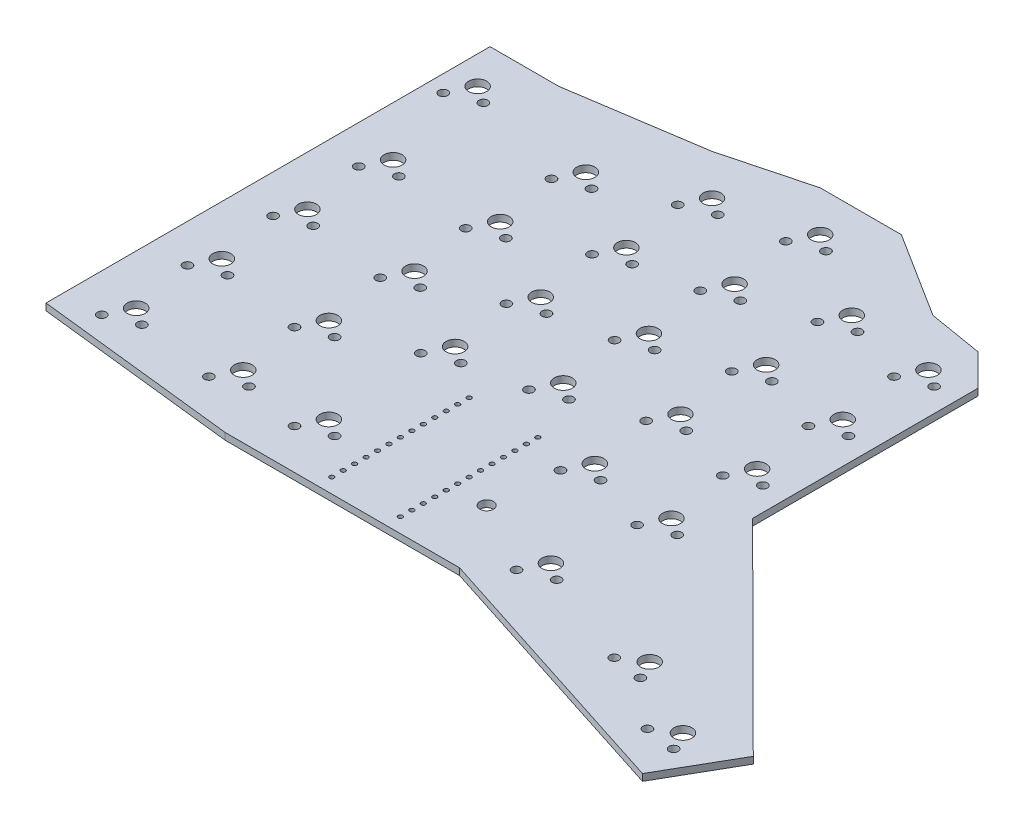
SolidWorks part; units mm, degrees
ref_plane "Front Plane" through (0, 0, 0) normal (0, 0, 1) x (1, 0, 0)
ref_plane "Top Plane" through (0, 0, 0) normal (0, 1, 0) x (1, 0, 0)
ref_plane "Right Plane" through (0, 0, 0) normal (1, 0, 0) x (0, 0, -1)
sketch "Main" plane through (0, 0, 0) normal (0, 1, 0) x (1, 0, 0)
  line L0 (6.46, 3.92) -> (12.81, 6.46) construction
  line L1 (0, 0) -> (18, 0) construction
  line L2 (0, 0) -> (0, 18) construction
  line L3 (0, 18) -> (18, 18) construction
  line L4 (18, 0) -> (18, 18) construction
  line L5 (2, 16) -> (16, 16)
  line L6 (2, 16) -> (2, 2)
  line L7 (2, 2) -> (16, 2)
  line L8 (16, 16) -> (16, 2)
  line L18 (9, 9) -> (6.46, 3.92) construction
  line L20 (9, 9) -> (12.81, 6.46) construction
  line L22 (25.46, 12.92) -> (31.81, 15.46) construction
  line L23 (19, 9) -> (37, 9) construction
  line L24 (19, 9) -> (19, 27) construction
  line L25 (19, 27) -> (37, 27) construction
  line L26 (37, 9) -> (37, 27) construction
  line L27 (21, 25) -> (35, 25)
  line L28 (21, 25) -> (21, 11)
  line L29 (21, 11) -> (35, 11)
  line L30 (35, 25) -> (35, 11)
  line L31 (28, 18) -> (25.46, 12.92) construction
  line L32 (28, 18) -> (31.81, 15.46) construction
  line L33 (44.46, 17.92) -> (50.81, 20.46) construction
  line L34 (38, 14) -> (56, 14) construction
  line L35 (38, 14) -> (38, 32) construction
  line L36 (38, 32) -> (56, 32) construction
  line L37 (56, 14) -> (56, 32) construction
  line L38 (40, 30) -> (54, 30)
  line L39 (40, 30) -> (40, 16)
  line L40 (40, 16) -> (54, 16)
  line L41 (54, 30) -> (54, 16)
  line L42 (47, 23) -> (44.46, 17.92) construction
  line L43 (47, 23) -> (50.81, 20.46) construction
  line L44 (63.46, 5.92) -> (69.81, 8.46) construction
  line L45 (57, 2) -> (75, 2) construction
  line L46 (57, 2) -> (57, 20) construction
  line L47 (57, 20) -> (75, 20) construction
  line L48 (75, 2) -> (75, 20) construction
  line L49 (59, 18) -> (73, 18)
  line L50 (59, 18) -> (59, 4)
  line L51 (59, 4) -> (73, 4)
  line L52 (73, 18) -> (73, 4)
  line L53 (66, 11) -> (63.46, 5.92) construction
  line L54 (66, 11) -> (69.81, 8.46) construction
  line L55 (82.46, 3.92) -> (88.81, 6.46) construction
  line L56 (76, 0) -> (94, 0) construction
  line L57 (76, 0) -> (76, 18) construction
  line L58 (76, 18) -> (94, 18) construction
  line L59 (94, 0) -> (94, 18) construction
  line L60 (78, 16) -> (92, 16)
  line L61 (78, 16) -> (78, 2)
  line L62 (78, 2) -> (92, 2)
  line L63 (92, 16) -> (92, 2)
  line L64 (85, 9) -> (82.46, 3.92) construction
  line L65 (85, 9) -> (88.81, 6.46) construction
  line L88 (2, -3) -> (16, -3)
  line L89 (2, -3) -> (2, -17)
  line L90 (2, -17) -> (16, -17)
  line L91 (16, -3) -> (16, -17)
  line L92 (21, 6) -> (35, 6)
  line L93 (21, 6) -> (21, -8)
  line L94 (21, -8) -> (35, -8)
  line L95 (35, 6) -> (35, -8)
  line L96 (40, 11) -> (54, 11)
  line L97 (40, 11) -> (40, -3)
  line L98 (40, -3) -> (54, -3)
  line L99 (54, 11) -> (54, -3)
  line L100 (59, -1) -> (73, -1)
  line L101 (59, -1) -> (59, -15)
  line L102 (59, -15) -> (73, -15)
  line L103 (73, -1) -> (73, -15)
  line L104 (78, -3) -> (92, -3)
  line L105 (78, -3) -> (78, -17)
  line L106 (78, -17) -> (92, -17)
  line L107 (92, -3) -> (92, -17)
  line L116 (6.46, -15.08) -> (12.81, -12.54) construction
  line L117 (0, -19) -> (18, -19) construction
  line L118 (0, -19) -> (0, -1) construction
  line L119 (0, -1) -> (18, -1) construction
  line L120 (18, -19) -> (18, -1) construction
  line L121 (9, -10) -> (6.46, -15.08) construction
  line L122 (9, -10) -> (12.81, -12.54) construction
  line L123 (25.46, -6.08) -> (31.81, -3.54) construction
  line L124 (19, -10) -> (37, -10) construction
  line L125 (19, -10) -> (19, 8) construction
  line L126 (19, 8) -> (37, 8) construction
  line L127 (37, -10) -> (37, 8) construction
  line L128 (28, -1) -> (25.46, -6.08) construction
  line L129 (28, -1) -> (31.81, -3.54) construction
  line L130 (44.46, -1.08) -> (50.81, 1.46) construction
  line L131 (38, -5) -> (56, -5) construction
  line L132 (38, -5) -> (38, 13) construction
  line L133 (38, 13) -> (56, 13) construction
  line L134 (56, -5) -> (56, 13) construction
  line L135 (47, 4) -> (44.46, -1.08) construction
  line L136 (47, 4) -> (50.81, 1.46) construction
  line L137 (63.46, -13.08) -> (69.81, -10.54) construction
  line L138 (57, -17) -> (75, -17) construction
  line L139 (57, -17) -> (57, 1) construction
  line L140 (57, 1) -> (75, 1) construction
  line L141 (75, -17) -> (75, 1) construction
  line L142 (66, -8) -> (63.46, -13.08) construction
  line L143 (66, -8) -> (69.81, -10.54) construction
  line L144 (82.46, -15.08) -> (88.81, -12.54) construction
  line L145 (76, -19) -> (94, -19) construction
  line L146 (76, -19) -> (76, -1) construction
  line L147 (76, -1) -> (94, -1) construction
  line L148 (94, -19) -> (94, -1) construction
  line L149 (85, -10) -> (82.46, -15.08) construction
  line L150 (85, -10) -> (88.81, -12.54) construction
  line L165 (2, -22) -> (16, -22)
  line L166 (2, -22) -> (2, -36)
  line L167 (2, -36) -> (16, -36)
  line L168 (16, -22) -> (16, -36)
  line L169 (21, -13) -> (35, -13)
  line L170 (21, -13) -> (21, -27)
  line L171 (21, -27) -> (35, -27)
  line L172 (35, -13) -> (35, -27)
  line L173 (40, -8) -> (54, -8)
  line L174 (40, -8) -> (40, -22)
  line L175 (40, -22) -> (54, -22)
  line L176 (54, -8) -> (54, -22)
  line L177 (59, -20) -> (73, -20)
  line L178 (59, -20) -> (59, -34)
  line L179 (59, -34) -> (73, -34)
  line L180 (73, -20) -> (73, -34)
  line L181 (78, -22) -> (92, -22)
  line L182 (78, -22) -> (78, -36)
  line L183 (78, -36) -> (92, -36)
  line L184 (92, -22) -> (92, -36)
  line L193 (6.46, -34.08) -> (12.81, -31.54) construction
  line L194 (0, -38) -> (18, -38) construction
  line L195 (0, -38) -> (0, -20) construction
  line L196 (0, -20) -> (18, -20) construction
  line L197 (18, -38) -> (18, -20) construction
  line L198 (9, -29) -> (6.46, -34.08) construction
  line L199 (9, -29) -> (12.81, -31.54) construction
  line L200 (25.46, -25.08) -> (31.81, -22.54) construction
  line L201 (19, -29) -> (37, -29) construction
  line L202 (19, -29) -> (19, -11) construction
  line L203 (19, -11) -> (37, -11) construction
  line L204 (37, -29) -> (37, -11) construction
  line L205 (28, -20) -> (25.46, -25.08) construction
  line L206 (28, -20) -> (31.81, -22.54) construction
  line L207 (44.46, -20.08) -> (50.81, -17.54) construction
  line L208 (38, -24) -> (56, -24) construction
  line L209 (38, -24) -> (38, -6) construction
  line L210 (38, -6) -> (56, -6) construction
  line L211 (56, -24) -> (56, -6) construction
  line L212 (47, -15) -> (44.46, -20.08) construction
  line L213 (47, -15) -> (50.81, -17.54) construction
  line L214 (63.46, -32.08) -> (69.81, -29.54) construction
  line L215 (57, -36) -> (75, -36) construction
  line L216 (57, -36) -> (57, -18) construction
  line L217 (57, -18) -> (75, -18) construction
  line L218 (75, -36) -> (75, -18) construction
  line L219 (66, -27) -> (63.46, -32.08) construction
  line L220 (66, -27) -> (69.81, -29.54) construction
  line L221 (82.46, -34.08) -> (88.81, -31.54) construction
  line L222 (76, -38) -> (94, -38) construction
  line L223 (76, -38) -> (76, -20) construction
  line L224 (76, -20) -> (94, -20) construction
  line L225 (94, -38) -> (94, -20) construction
  line L226 (85, -29) -> (82.46, -34.08) construction
  line L227 (85, -29) -> (88.81, -31.54) construction
  line L242 (2, -41) -> (16, -41)
  line L243 (2, -41) -> (2, -55)
  line L244 (2, -55) -> (16, -55)
  line L245 (16, -41) -> (16, -55)
  line L246 (21, -32) -> (35, -32)
  line L247 (21, -32) -> (21, -46)
  line L248 (21, -46) -> (35, -46)
  line L249 (35, -32) -> (35, -46)
  line L250 (40, -27) -> (54, -27)
  line L251 (40, -27) -> (40, -41)
  line L252 (40, -41) -> (54, -41)
  line L253 (54, -27) -> (54, -41)
  line L254 (59, -39) -> (73, -39)
  line L255 (59, -39) -> (59, -53)
  line L256 (59, -53) -> (73, -53)
  line L257 (73, -39) -> (73, -53)
  line L258 (78, -41) -> (92, -41)
  line L259 (78, -41) -> (78, -55)
  line L260 (78, -55) -> (92, -55)
  line L261 (92, -41) -> (92, -55)
  line L270 (6.46, -53.08) -> (12.81, -50.54) construction
  line L271 (0, -57) -> (18, -57) construction
  line L272 (0, -57) -> (0, -39) construction
  line L273 (0, -39) -> (18, -39) construction
  line L274 (18, -57) -> (18, -39) construction
  line L275 (9, -48) -> (6.46, -53.08) construction
  line L276 (9, -48) -> (12.81, -50.54) construction
  line L277 (25.46, -44.08) -> (31.81, -41.54) construction
  line L278 (19, -48) -> (37, -48) construction
  line L279 (19, -48) -> (19, -30) construction
  line L280 (19, -30) -> (37, -30) construction
  line L281 (37, -48) -> (37, -30) construction
  line L282 (28, -39) -> (25.46, -44.08) construction
  line L283 (28, -39) -> (31.81, -41.54) construction
  line L284 (44.46, -39.08) -> (50.81, -36.54) construction
  line L285 (38, -43) -> (56, -43) construction
  line L286 (38, -43) -> (38, -25) construction
  line L287 (38, -25) -> (56, -25) construction
  line L288 (56, -43) -> (56, -25) construction
  line L289 (47, -34) -> (44.46, -39.08) construction
  line L290 (47, -34) -> (50.81, -36.54) construction
  line L291 (63.46, -51.08) -> (69.81, -48.54) construction
  line L292 (57, -55) -> (75, -55) construction
  line L293 (57, -55) -> (57, -37) construction
  line L294 (57, -37) -> (75, -37) construction
  line L295 (75, -55) -> (75, -37) construction
  line L296 (66, -46) -> (63.46, -51.08) construction
  line L297 (66, -46) -> (69.81, -48.54) construction
  line L298 (82.46, -53.08) -> (88.81, -50.54) construction
  line L299 (76, -57) -> (94, -57) construction
  line L300 (76, -57) -> (76, -39) construction
  line L301 (76, -39) -> (94, -39) construction
  line L302 (94, -57) -> (94, -39) construction
  line L303 (85, -48) -> (82.46, -53.08) construction
  line L304 (85, -48) -> (88.81, -50.54) construction
  line L312 (6.46, -72.08) -> (12.81, -69.54) construction
  line L313 (0, -76) -> (18, -76) construction
  line L314 (0, -76) -> (0, -58) construction
  line L315 (0, -58) -> (18, -58) construction
  line L316 (18, -76) -> (18, -58) construction
  line L317 (2, -60) -> (16, -60)
  line L318 (2, -60) -> (2, -74)
  line L323 (21, -60) -> (35, -60)
  line L324 (21, -60) -> (21, -74)
  line L325 (21, -74) -> (35, -74)
  line L326 (35, -60) -> (35, -74)
  line L327 (25.46, -72.08) -> (31.81, -69.54) construction
  line L328 (19, -76) -> (37, -76) construction
  line L329 (19, -76) -> (19, -58) construction
  line L330 (-22.04, 8.42) -> (-15.69, 10.96) construction
  line L331 (-28.5, 4.5) -> (-10.5, 4.5) construction
  line L332 (-28.5, 4.5) -> (-28.5, 22.5) construction
  line L333 (-28.5, 22.5) -> (-10.5, 22.5) construction
  line L334 (-10.5, 4.5) -> (-10.5, 22.5) construction
  line L335 (-26.5, 20.5) -> (-12.5, 20.5)
  line L336 (-26.5, 20.5) -> (-26.5, 6.5)
  line L337 (-26.5, 6.5) -> (-12.5, 6.5)
  line L338 (-12.5, 20.5) -> (-12.5, 6.5)
  line L339 (-19.5, 13.5) -> (-22.04, 8.42) construction
  line L340 (-19.5, 13.5) -> (-15.69, 10.96) construction
  line L341 (-21.75, -41) -> (-7.75, -41)
  line L342 (-21.75, -41) -> (-21.75, -55)
  line L343 (-21.75, -55) -> (-7.75, -55)
  line L344 (-7.75, -41) -> (-7.75, -55)
  line L345 (-17.29, -53.08) -> (-10.94, -50.54) construction
  line L346 (-28.5, -57) -> (-1, -57) construction
  line L347 (-28.5, -57) -> (-28.5, -39) construction
  line L348 (-28.5, -39) -> (-1, -39) construction
  line L349 (-1, -57) -> (-1, -39) construction
  line L350 (-14.75, -48) -> (-17.29, -53.08) construction
  line L351 (-14.75, -48) -> (-10.94, -50.54) construction
  line L352 (-21.75, -22) -> (-7.75, -22)
  line L353 (-21.75, -22) -> (-21.75, -36)
  line L354 (2, -74) -> (16, -74)
  line L355 (16, -60) -> (16, -74)
  line L356 (9, -67) -> (6.46, -72.08) construction
  line L357 (9, -67) -> (12.81, -69.54) construction
  line L358 (-17.29, -72.08) -> (-10.94, -69.54) construction
  line L359 (-28.5, -76) -> (-1, -76) construction
  line L360 (-28.5, -76) -> (-28.5, -58) construction
  line L361 (-28.5, -58) -> (-1, -58) construction
  line L362 (-1, -76) -> (-1, -58) construction
  line L363 (-21.75, -60) -> (-7.75, -60)
  line L364 (-21.75, -60) -> (-21.75, -74)
  line L365 (-21.75, -74) -> (-7.75, -74)
  line L366 (-7.75, -60) -> (-7.75, -74)
  line L367 (-14.75, -67) -> (-17.29, -72.08) construction
  line L368 (-14.75, -67) -> (-10.94, -69.54) construction
  line L369 (-21.75, -36) -> (-7.75, -36)
  line L370 (-7.75, -22) -> (-7.75, -36)
  line L371 (-17.29, -34.08) -> (-10.94, -31.54) construction
  line L372 (-28.5, -38) -> (-1, -38) construction
  line L373 (-28.5, -38) -> (-28.5, -20) construction
  line L374 (-28.5, -20) -> (-1, -20) construction
  line L375 (-1, -38) -> (-1, -20) construction
  line L376 (-14.75, -29) -> (-17.29, -34.08) construction
  line L377 (-14.75, -29) -> (-10.94, -31.54) construction
  line L378 (-21.75, -3) -> (-7.75, -3)
  line L379 (-21.75, -3) -> (-21.75, -17)
  line L380 (-21.75, -17) -> (-7.75, -17)
  line L381 (-7.75, -3) -> (-7.75, -17)
  line L382 (-17.29, -15.08) -> (-10.94, -12.54) construction
  line L383 (-28.5, -19) -> (-1, -19) construction
  line L384 (-28.5, -19) -> (-28.5, -1) construction
  line L385 (-28.5, -1) -> (-1, -1) construction
  line L386 (-1, -19) -> (-1, -1) construction
  line L387 (-14.75, -10) -> (-17.29, -15.08) construction
  line L388 (-14.75, -10) -> (-10.94, -12.54) construction
  line L393 (109.2068, -61.578) -> (124.8116, -70.5498) construction
  line L394 (109.2068, -61.578) -> (95.5, -85.4186) construction
  line L398 (124.8116, -70.5498) -> (111.1047, -94.3903) construction
  line L402 (77.71, -75.08) -> (84.06, -72.54) construction
  line L403 (66.5, -79) -> (94, -79) construction
  line L404 (66.5, -79) -> (66.5, -61) construction
  line L405 (66.5, -61) -> (94, -61) construction
  line L406 (94, -79) -> (94, -61) construction
  line L407 (73.25, -63) -> (87.25, -63)
  line L408 (73.25, -63) -> (73.25, -77)
  line L409 (73.25, -77) -> (87.25, -77)
  line L410 (87.25, -63) -> (87.25, -77)
  line L411 (80.25, -70) -> (77.71, -75.08) construction
  line L412 (80.25, -70) -> (84.06, -72.54) construction
  line L413 (95.5, -85.4186) -> (111.1047, -94.3903) construction
  line L414 (95.5, -85.4186) -> (124.8116, -70.5498) construction
  line L415 (80.25, -130) -> (110.1558, -77.9842) construction
  line L416 (107.5763, -68.4267) -> (119.7133, -75.4047)
  line L417 (107.5763, -68.4267) -> (100.5983, -80.5637)
  line L418 (119.7133, -75.4047) -> (112.7353, -87.5417)
  line L419 (100.5983, -80.5637) -> (112.7353, -87.5417)
  line L420 (107.5763, -68.4267) -> (112.7353, -87.5417) construction
  line L421 (105.4217, -81.1221) -> (110.1558, -77.9842) construction
  line L422 (110.1558, -77.9842) -> (112.1927, -82.0853) construction
  line L423 (112.1927, -82.0853) -> (105.4217, -81.1221) construction
  line L424 (126.5454, -71.5466) -> (142.1502, -80.5184) construction
  line L425 (126.5454, -71.5466) -> (112.8386, -95.3872) construction
  line L426 (142.1502, -80.5184) -> (128.4433, -104.3589) construction
  line L427 (112.8386, -95.3872) -> (128.4433, -104.3589) construction
  line L428 (112.8386, -95.3872) -> (142.1502, -80.5184) construction
  line L430 (124.9149, -78.3953) -> (137.0519, -85.3733)
  line L431 (124.9149, -78.3953) -> (117.9369, -90.5323)
  line L432 (137.0519, -85.3733) -> (130.0739, -97.5103)
  line L433 (117.9369, -90.5323) -> (130.0739, -97.5103)
  line L434 (124.9149, -78.3953) -> (130.0739, -97.5103) construction
  line L435 (122.7603, -91.0907) -> (127.4944, -87.9528) construction
  line L436 (127.4944, -87.9528) -> (129.5313, -92.0539) construction
  line L437 (129.5313, -92.0539) -> (122.7603, -91.0907) construction
  line L448 (19, -58) -> (37, -58) construction
  line L449 (37, -76) -> (37, -58) construction
  line L450 (28, -67) -> (25.46, -72.08) construction
  line L451 (28, -67) -> (31.81, -69.54) construction
  circle A0 centre (9, 9) radius 2 construction
  circle A1 centre (6.46, 3.92) radius 1.5 construction
  circle A2 centre (12.81, 6.46) radius 1.5 construction
  circle A6 centre (28, 18) radius 2 construction
  circle A7 centre (25.46, 12.92) radius 1.5 construction
  circle A8 centre (31.81, 15.46) radius 1.5 construction
  circle A9 centre (47, 23) radius 2 construction
  circle A10 centre (44.46, 17.92) radius 1.5 construction
  circle A11 centre (50.81, 20.46) radius 1.5 construction
  circle A12 centre (66, 11) radius 2 construction
  circle A13 centre (63.46, 5.92) radius 1.5 construction
  circle A14 centre (69.81, 8.46) radius 1.5 construction
  circle A15 centre (85, 9) radius 2 construction
  circle A16 centre (82.46, 3.92) radius 1.5 construction
  circle A17 centre (88.81, 6.46) radius 1.5 construction
  circle A24 centre (9, -10) radius 2 construction
  circle A25 centre (6.46, -15.08) radius 1.5 construction
  circle A26 centre (12.81, -12.54) radius 1.5 construction
  circle A27 centre (28, -1) radius 2 construction
  circle A28 centre (25.46, -6.08) radius 1.5 construction
  circle A29 centre (31.81, -3.54) radius 1.5 construction
  circle A30 centre (47, 4) radius 2 construction
  circle A31 centre (44.46, -1.08) radius 1.5 construction
  circle A32 centre (50.81, 1.46) radius 1.5 construction
  circle A33 centre (66, -8) radius 2 construction
  circle A34 centre (63.46, -13.08) radius 1.5 construction
  circle A35 centre (69.81, -10.54) radius 1.5 construction
  circle A36 centre (85, -10) radius 2 construction
  circle A37 centre (82.46, -15.08) radius 1.5 construction
  circle A38 centre (88.81, -12.54) radius 1.5 construction
  circle A45 centre (9, -29) radius 2 construction
  circle A46 centre (6.46, -34.08) radius 1.5 construction
  circle A47 centre (12.81, -31.54) radius 1.5 construction
  circle A48 centre (28, -20) radius 2 construction
  circle A49 centre (25.46, -25.08) radius 1.5 construction
  circle A50 centre (31.81, -22.54) radius 1.5 construction
  circle A51 centre (47, -15) radius 2 construction
  circle A52 centre (44.46, -20.08) radius 1.5 construction
  circle A53 centre (50.81, -17.54) radius 1.5 construction
  circle A54 centre (66, -27) radius 2 construction
  circle A55 centre (63.46, -32.08) radius 1.5 construction
  circle A56 centre (69.81, -29.54) radius 1.5 construction
  circle A57 centre (85, -29) radius 2 construction
  circle A58 centre (82.46, -34.08) radius 1.5 construction
  circle A59 centre (88.81, -31.54) radius 1.5 construction
  circle A63 centre (9, -67) radius 2 construction
  circle A64 centre (6.46, -72.08) radius 1.5 construction
  circle A65 centre (12.81, -69.54) radius 1.5 construction
  circle A66 centre (9, -48) radius 2 construction
  circle A67 centre (6.46, -53.08) radius 1.5 construction
  circle A68 centre (12.81, -50.54) radius 1.5 construction
  circle A69 centre (28, -39) radius 2 construction
  circle A70 centre (25.46, -44.08) radius 1.5 construction
  circle A71 centre (31.81, -41.54) radius 1.5 construction
  circle A72 centre (47, -34) radius 2 construction
  circle A73 centre (44.46, -39.08) radius 1.5 construction
  circle A74 centre (50.81, -36.54) radius 1.5 construction
  circle A75 centre (66, -46) radius 2 construction
  circle A76 centre (63.46, -51.08) radius 1.5 construction
  circle A77 centre (69.81, -48.54) radius 1.5 construction
  circle A78 centre (85, -48) radius 2 construction
  circle A79 centre (82.46, -53.08) radius 1.5 construction
  circle A80 centre (88.81, -50.54) radius 1.5 construction
  circle A81 centre (-14.75, -67) radius 2 construction
  circle A82 centre (-17.29, -72.08) radius 1.5 construction
  circle A83 centre (-10.94, -69.54) radius 1.5 construction
  circle A84 centre (28, -67) radius 2 construction
  circle A85 centre (25.46, -72.08) radius 1.5 construction
  circle A86 centre (31.81, -69.54) radius 1.5 construction
  circle A87 centre (-19.5, 13.5) radius 2 construction
  circle A88 centre (-22.04, 8.42) radius 1.5 construction
  circle A89 centre (-15.69, 10.96) radius 1.5 construction
  circle A90 centre (-14.75, -48) radius 2 construction
  circle A91 centre (-17.29, -53.08) radius 1.5 construction
  circle A92 centre (-10.94, -50.54) radius 1.5 construction
  circle A93 centre (-14.75, -29) radius 2 construction
  circle A94 centre (-17.29, -34.08) radius 1.5 construction
  circle A95 centre (-10.94, -31.54) radius 1.5 construction
  circle A96 centre (-14.75, -10) radius 2 construction
  circle A97 centre (-17.29, -15.08) radius 1.5 construction
  circle A98 centre (-10.94, -12.54) radius 1.5 construction
  circle A102 centre (80.25, -70) radius 2 construction
  circle A103 centre (77.71, -75.08) radius 1.5 construction
  circle A104 centre (84.06, -72.54) radius 1.5 construction
  circle A105 centre (80.25, -130) radius 60 construction
  circle A106 centre (110.1558, -77.9842) radius 2 construction
  circle A107 centre (105.4217, -81.1221) radius 1.5 construction
  circle A108 centre (112.1927, -82.0853) radius 1.5 construction
  circle A109 centre (127.4944, -87.9528) radius 2 construction
  circle A110 centre (122.7603, -91.0907) radius 1.5 construction
  circle A111 centre (129.5313, -92.0539) radius 1.5 construction
  point P9 (9, 16)
  point P10 (9, 18)
  point P11 (2, 9)
  point P12 (0, 9)
  point P30 (28, 25)
  point P31 (28, 27)
  point P32 (21, 18)
  point P33 (19, 18)
  point P46 (47, 30)
  point P47 (47, 32)
  point P48 (40, 23)
  point P49 (38, 23)
  point P64 (66, 18)
  point P65 (66, 20)
  point P66 (59, 11)
  point P67 (57, 11)
  point P82 (85, 16)
  point P83 (85, 18)
  point P84 (78, 9)
  point P85 (76, 9)
  point P102 (9, -60)
  point P103 (9, -58)
  point P104 (2, -67)
  point P105 (0, -67)
  point P124 (-14.75, -60)
  point P125 (-14.75, -58)
  point P126 (-21.75, -67)
  point P127 (-28.5, -67)
  point P297 (-19.5, 20.5)
  point P298 (-19.5, 22.5)
  point P299 (-26.5, 13.5)
  point P300 (-28.5, 13.5)
  point P423 (103.3024, -89.9045)
  point P444 (80.25, -63)
  point P445 (80.25, -61)
  point P446 (73.25, -70)
  point P447 (66.5, -70)
  dimension "D6" = 4
  dimension "D7" = 3
  dimension "D10" = 1
  dimension "D11" = 12
  dimension "D21" = 9.5
  dimension "D22" = 1.5
  dimension "D26" = 120
  dimension "D38" = 21.8
  dimension "D1" = 18
  dimension "D2" = 14
  dimension "D3" = 3.81
  dimension "D4" = 2.54
  dimension "D5" = 2.54
  dimension "D8" = 1
  dimension "D9" = 5
  dimension "D12" = 1
  dimension "D13" = 9
  dimension "D14" = 1
  dimension "D15" = 2
  dimension "D16" = 2
  dimension "D17" = 27.5
  dimension "D18" = 1
  dimension "D20" = 1
  dimension "D24" = 1
  dimension "D25" = 8
  dimension "D27" = 2
  dimension "D28" = 5.08
  dimension "D29" = 2.54
  dimension "D30" = 2.54
  dimension "D31" = 2.54
  dimension "D32" = 2.54
  dimension "D33" = 2.54
  dimension "D34" = 2.54
  dimension "D35" = 2.54
  dimension "D36" = 2.54
  dimension "D37" = 21.8
  dimension "D19" = 4
  dimension "D23" = 4
sketch "Sketch1" plane through (0, 0, 0) normal (0, 1, 0) x (1, 0, 0)
  line L7 (87, 18) -> (94, 11)
  line L8 (115.2061, -91.2693) -> (124.1779, -75.6645) construction
  line L9 (76, 18) -> (94, 18) construction
  line L10 (94, 0) -> (94, 18) construction
  line L12 (115.2061, -91.2693) -> (130.8109, -100.241) construction
  line L14 (124.1779, -75.6645) -> (139.7826, -84.6363) construction
  line L18 (130.8109, -100.241) -> (139.7826, -84.6363)
  line L19 (115.2061, -91.2693) -> (139.7826, -84.6363) construction
  line L20 (124.1779, -75.6645) -> (130.8109, -100.241) construction
  line L23 (142.1502, -80.5184) -> (128.4433, -104.3589) construction
  line L27 (71, -81) -> (130.8109, -100.241)
  line L28 (139.7826, -84.6363) -> (94, -39)
  line L29 (94, -39) -> (94, 11)
  line L30 (87, 18) -> (75, 20)
  line L31 (75, 20) -> (56, 32)
  line L32 (56, 32) -> (38, 32)
  line L33 (38, 32) -> (19, 27)
  line L34 (19, 27) -> (-10.5, 22.5)
  line L35 (-10.5, 22.5) -> (-25.75, 22.5)
  line L38 (19, -81) -> (71, -81)
  line L165 (66.5, -79) -> (94, -79) construction
  line L167 (19, -76) -> (19, -58) construction
  line L168 (75, -55) -> (75, -37) construction
  line L169 (-28.5, -76) -> (-1, -76) construction
  line L174 (-23.75, -58) -> (-5.75, -58) construction
  line L175 (-23.75, -58) -> (-23.75, -76) construction
  line L176 (-23.75, -76) -> (-5.75, -76) construction
  line L177 (-5.75, -58) -> (-5.75, -76) construction
  line L178 (-23.75, -58) -> (-5.75, -76) construction
  line L179 (-23.75, -76) -> (-5.75, -58) construction
  line L181 (19, -81) -> (-25.75, -76)
  line L182 (-25.75, -76) -> (-25.75, 22.5)
  point P1 (127.4944, -87.9528)
  point P10 (86.857, 18)
  point P24 (-14.75, -67)
  dimension "D2" = 98.5203
  dimension "D7" = 64.643
  dimension "D8" = 7
  dimension "D3" = 43.0414
  dimension "D4" = 52
  dimension "D5" = 62.8296
  dimension "D6" = 18
  dimension "D9" = 7
  dimension "D10" = 22.4722
  dimension "D11" = 18
  dimension "D12" = 19.6469
  dimension "D13" = 29.8412
  dimension "D14" = 15.25
  dimension "D15" = 4
  dimension "D16" = 2
  dimension "D17" = 11
extrude "Boss-Extrude1" add sketch "Sketch1" against normal blind 1.5
sketch "Sketch2" plane through (0, 0, 0) normal (0, 1, 0) x (1, 0, 0)
  line L0 (47, -34) -> (47, -81) construction
  line L1 (19, -81) -> (71, -81) construction
  circle A0 centre (39.38, -77.75) radius 0.5
  circle A1 centre (39.38, -75.21) radius 0.5
  circle A2 centre (39.38, -72.67) radius 0.5
  circle A3 centre (39.38, -70.13) radius 0.5
  circle A4 centre (39.38, -67.59) radius 0.5
  circle A5 centre (39.38, -65.05) radius 0.5
  circle A6 centre (39.38, -62.51) radius 0.5
  circle A7 centre (39.38, -59.97) radius 0.5
  circle A8 centre (39.38, -57.43) radius 0.5
  circle A9 centre (39.38, -54.89) radius 0.5
  circle A10 centre (39.38, -52.35) radius 0.5
  circle A11 centre (39.38, -49.81) radius 0.5
  circle A12 centre (39.38, -47.27) radius 0.5
  circle A13 centre (54.62, -47.27) radius 0.5
  circle A14 centre (54.62, -49.81) radius 0.5
  circle A15 centre (54.62, -52.35) radius 0.5
  circle A16 centre (54.62, -54.89) radius 0.5
  circle A17 centre (54.62, -57.43) radius 0.5
  circle A18 centre (54.62, -59.97) radius 0.5
  circle A19 centre (54.62, -62.51) radius 0.5
  circle A20 centre (54.62, -65.05) radius 0.5
  circle A21 centre (54.62, -67.59) radius 0.5
  circle A22 centre (54.62, -70.13) radius 0.5
  circle A23 centre (54.62, -72.67) radius 0.5
  circle A24 centre (54.62, -75.21) radius 0.5
  circle A25 centre (54.62, -77.75) radius 0.5
  circle A26 centre (62, -66) radius 1.5
  dimension "D2" = 1
  dimension "D8" = 3
  dimension "D1" = 43.75
  dimension "D3" = 7.62
  dimension "D5" = 2.54
  dimension "D6" = 32
  dimension "D7" = 15
  dimension "D4" = 13
extrude "Cut-Extrude1" cut sketch "Sketch2" against normal through all
sketch "Sketch3" plane through (0, 0, 0) normal (0, 1, 0) x (1, 0, 0)
  line L0 (80.25, -70) -> (77.71, -75.08) construction
  line L1 (112.8386, -95.3872) -> (142.1502, -80.5184) construction
  circle A0 centre (-19.5, 13.5) radius 2
  circle A1 centre (9, 9) radius 2
  circle A2 centre (28, 18) radius 2
  circle A3 centre (47, 23) radius 2
  circle A4 centre (66, 11) radius 2
  circle A5 centre (85, 9) radius 2
  circle A6 centre (-14.75, -10) radius 2
  circle A7 centre (9, -10) radius 2
  circle A8 centre (28, -1) radius 2
  circle A9 centre (47, 4) radius 2
  circle A10 centre (66, -8) radius 2
  circle A11 centre (85, -10) radius 2
  circle A12 centre (47, -15) radius 2
  circle A13 centre (-14.75, -29) radius 2
  circle A14 centre (-14.75, -48) radius 2
  circle A15 centre (-14.75, -67) radius 2
  circle A16 centre (9, -29) radius 2
  circle A17 centre (9, -48) radius 2
  circle A18 centre (9, -67) radius 2
  circle A19 centre (28, -67) radius 2
  circle A20 centre (28, -39) radius 2
  circle A21 centre (28, -20) radius 2
  circle A22 centre (47, -34) radius 2
  circle A23 centre (66, -27) radius 2
  circle A24 centre (85, -29) radius 2
  circle A25 centre (85, -48) radius 2
  circle A26 centre (66, -46) radius 2
  circle A27 centre (80.25, -70) radius 2
  circle A28 centre (110.1558, -77.9842) radius 2
  circle A29 centre (127.4944, -87.9528) radius 2
  circle A30 centre (-19.5, 13.5) radius 2 construction
extrude "Cut-Extrude2" cut sketch "Sketch3" against normal through all
sketch "Sketch4" plane through (0, 0, 0) normal (0, 1, 0) x (1, 0, 0)
  circle A0 centre (-22.04, 8.42) radius 1
  circle A1 centre (-15.69, 10.96) radius 1
  circle A2 centre (-10.94, -12.54) radius 1
  circle A3 centre (-17.29, -15.08) radius 1
  circle A4 centre (-10.94, -31.54) radius 1
  circle A5 centre (-17.29, -34.08) radius 1
  circle A6 centre (-10.94, -50.54) radius 1
  circle A7 centre (-17.29, -53.08) radius 1
  circle A8 centre (-17.29, -72.08) radius 1
  circle A9 centre (-10.94, -69.54) radius 1
  circle A10 centre (6.46, -72.08) radius 1
  circle A11 centre (12.81, -69.54) radius 1
  circle A12 centre (25.46, -72.08) radius 1
  circle A13 centre (31.81, -69.54) radius 1
  circle A14 centre (6.46, -53.08) radius 1
  circle A15 centre (12.81, -50.54) radius 1
  circle A16 centre (6.46, -34.08) radius 1
  circle A17 centre (12.81, -31.54) radius 1
  circle A18 centre (25.46, -44.08) radius 1
  circle A19 centre (31.81, -41.54) radius 1
  circle A20 centre (25.46, -25.08) radius 1
  circle A21 centre (31.81, -22.54) radius 1
  circle A22 centre (6.46, -15.08) radius 1
  circle A23 centre (12.81, -12.54) radius 1
  circle A24 centre (6.46, 3.92) radius 1
  circle A25 centre (12.81, 6.46) radius 1
  circle A26 centre (25.46, 12.92) radius 1
  circle A27 centre (31.81, 15.46) radius 1
  circle A28 centre (25.46, -6.08) radius 1
  circle A29 centre (31.81, -3.54) radius 1
  circle A30 centre (44.46, 17.92) radius 1
  circle A31 centre (50.81, 20.46) radius 1
  circle A32 centre (44.46, -1.08) radius 1
  circle A33 centre (50.81, 1.46) radius 1
  circle A34 centre (44.46, -20.08) radius 1
  circle A35 centre (50.81, -17.54) radius 1
  circle A36 centre (44.46, -39.08) radius 1
  circle A37 centre (50.81, -36.54) radius 1
  circle A38 centre (69.81, 8.46) radius 1
  circle A39 centre (63.46, 5.92) radius 1
  circle A40 centre (82.46, 3.92) radius 1
  circle A41 centre (88.81, 6.46) radius 1
  circle A42 centre (69.81, -10.54) radius 1
  circle A43 centre (63.46, -13.08) radius 1
  circle A44 centre (82.46, -15.08) radius 1
  circle A45 centre (88.81, -12.54) radius 1
  circle A46 centre (63.46, -32.08) radius 1
  circle A47 centre (69.81, -29.54) radius 1
  circle A48 centre (63.46, -51.08) radius 1
  circle A49 centre (69.81, -48.54) radius 1
  circle A50 centre (82.46, -34.08) radius 1
  circle A51 centre (88.81, -31.54) radius 1
  circle A52 centre (88.81, -50.54) radius 1
  circle A53 centre (82.46, -53.08) radius 1
  circle A54 centre (77.71, -75.08) radius 1
  circle A55 centre (84.06, -72.54) radius 1
  circle A56 centre (105.4217, -81.1221) radius 1
  circle A57 centre (112.1927, -82.0853) radius 1
  circle A58 centre (122.7603, -91.0907) radius 1
  circle A59 centre (129.5313, -92.0539) radius 1
  dimension "D1" = 2
extrude "Cut-Extrude3" cut sketch "Sketch4" against normal through all
